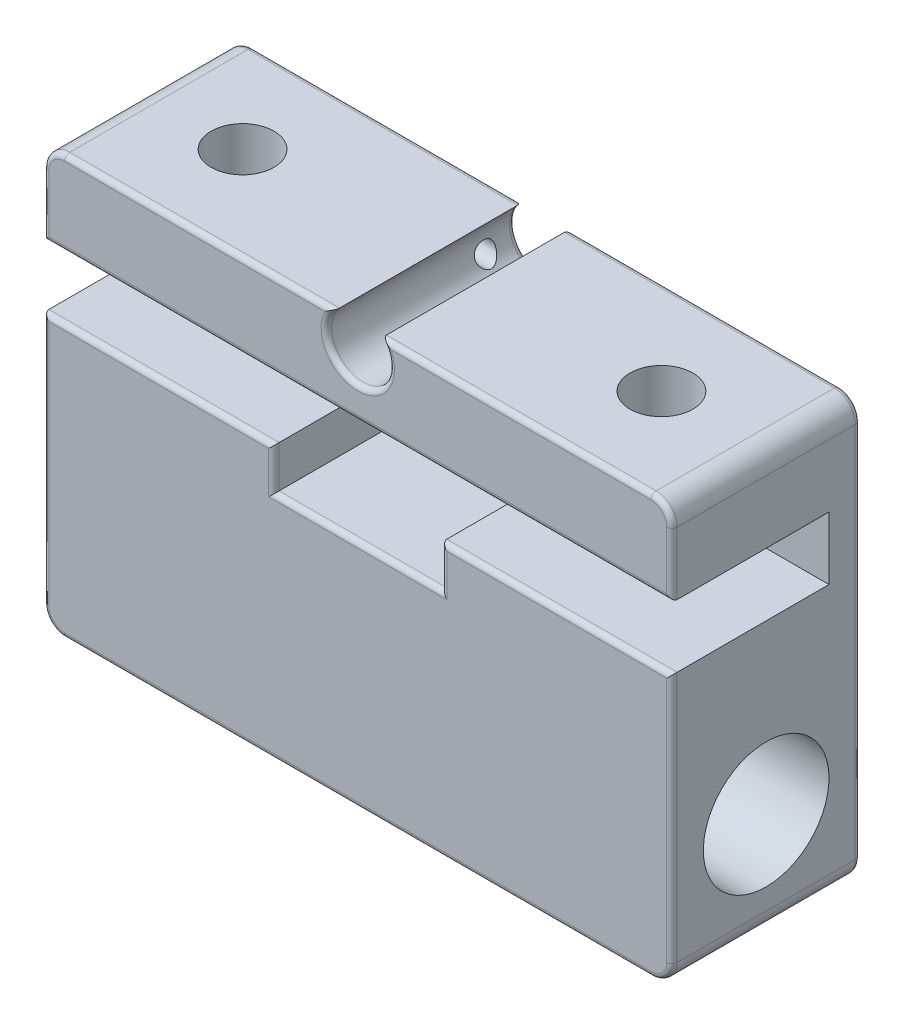
SolidWorks part; units mm, degrees
ref_plane "Front Plane" through (0, 0, 0) normal (0, 0, 1) x (1, 0, 0)
ref_plane "Top Plane" through (0, 0, 0) normal (0, 1, 0) x (1, 0, 0)
ref_plane "Right Plane" through (0, 0, 0) normal (1, 0, 0) x (0, 0, -1)
sketch "Sketch1" plane through (0, 0, 0) normal (0, 0, 1) x (1, 0, 0)
  line L1 (-30, 20) -> (30, 20)
  line L2 (-30, 20) -> (-30, -20)
  line L3 (-30, -20) -> (30, -20)
  line L4 (30, 20) -> (30, -20)
  line L5 (-30, 20) -> (30, -20) construction
  line L6 (-30, -20) -> (30, 20) construction
  point P0 (0, 0)
  dimension "D1" = 40
  dimension "D2" = 60
extrude "Boss-Extrude1" add sketch "Sketch1" along normal mid plane 18
sketch "Sketch2" plane through (-30, 0, 0) normal (-1, 0, 0) x (0, 0, 1)
  line L0 (0, 1.8022) -> (0, -4.9662) construction
  circle A0 centre (0, -10) radius 6
  dimension "D1" = 12
  dimension "D2" = 10
extrude "Cut-Extrude1" cut sketch "Sketch2" against normal through all
sketch "Sketch3" plane through (0, 0, 9) normal (0, 0, 1) x (1, 0, 0)
  line L0 (0, 0) -> (0, 7.3584) construction
  line L4 (30, -20) -> (30, 20)
  line L5 (30, 20) -> (-30, 20)
  line L6 (-30, 20) -> (-30, -20)
  line L7 (-30, -20) -> (30, -20)
  line L8 (30, -20) -> (30, 20) construction
  line L9 (30, 20) -> (-30, 20) construction
  line L10 (-30, 20) -> (-30, -20) construction
  line L11 (-30, -20) -> (30, -20) construction
  circle A0 centre (0, 18) radius 3
  point P7 (0, 0)
  dimension "D2" = 6
  dimension "D3" = 18
  dimension "D1" = 0
extrude "Cut-Extrude2" cut sketch "Sketch3" against normal through all
sketch "Sketch4" plane through (0, 0, 9) normal (0, 0, 1) x (1, 0, 0)
  line L0 (-30, 20) -> (-30, -20) construction
  line L1 (-30, 12) -> (30, 12)
  line L2 (-30, 12) -> (-30, 6)
  line L3 (-30, 6) -> (-8, 6)
  line L4 (30, 12) -> (30, 6)
  line L5 (30, -20) -> (30, 20) construction
  line L6 (8, 6) -> (30, 6)
  line L8 (-8, 6) -> (-8, 2)
  line L9 (-8, 2) -> (8, 2)
  line L10 (8, 6) -> (8, 2)
  dimension "D1" = 6
  dimension "D2" = 16
  dimension "D3" = 8
  dimension "D4" = 12
  dimension "D5" = 4
extrude "Cut-Extrude3" cut sketch "Sketch4" against normal blind 15
sketch "Sketch5" plane through (-30, 0, 0) normal (-1, 0, 0) x (0, 0, 1)
  line L0 (9, 20) -> (9, 12) construction
  line L1 (9, 20) -> (-9, 20) construction
  circle A0 centre (-6, 17) radius 1
  dimension "D1" = 2
  dimension "D2" = 15
  dimension "D3" = 3
extrude "Cut-Extrude4" cut sketch "Sketch5" against normal blind 29
sketch "Sketch6" plane through (-30, 0, 0) normal (-1, 0, 0) x (0, 0, 1)
  circle A0 centre (-6, 17) radius 1.5
  dimension "D1" = 3
extrude "Cut-Extrude5" cut sketch "Sketch6" against normal blind 5
sketch "Sketch7" plane through (0, 20, 0) normal (0, 1, 0) x (1, 0, 0)
  line L0 (-7.4904, 0) -> (6.3865, 0) construction
  line L1 (0, 5.874) -> (0, -4.849) construction
  circle A0 centre (-20, 0) radius 2
  circle A1 centre (20, 0) radius 2
  point P9 (0, 0)
  dimension "D1" = 4
  dimension "D2" = 20
extrude "Cut-Extrude6" cut sketch "Sketch7" against normal up to next
sketch "Sketch8" plane through (0, 20, 0) normal (0, 1, 0) x (1, 0, 0)
  line L0 (0, 5.0067) -> (0, -4.6125) construction
  circle A0 centre (-20, 0) radius 3
  circle A1 centre (20, 0) radius 3
  dimension "D1" = 6
extrude "Cut-Extrude7" cut sketch "Sketch8" against normal blind 5
fillet "Fillet1" radius 2 4 edges at (30, -20, 0) (30, 20, 0) (-30, -20, 0) (-30, 20, 0)
fillet "Fillet2" radius 0.5 28 edges at (29.4142, 19.4142, -9) (15.118, 20, -9) (0, 15, -9) (-15.118, 20, -9) (-29.4142, 19.4142, -9) (-30, 0, -9) (-29.4142, -19.4142, -9) (0, -20, -9) (29.4142, -19.4142, -9) (30, 0, -9) (-29.4142, -19.4142, 9) (-30, -6, 9) (-19, 6, 9) (-8, 4, 9) (0, 2, 9) (8, 4, 9) (19, 6, 9) (30, -6, 9) (29.4142, -19.4142, 9) (0, -20, 9) (0, 12, 9) (-30, 15, 9) (-29.4142, 19.4142, 9) (-15.118, 20, 9) (0, 15, 9) (15.118, 20, 9) (29.4142, 19.4142, 9) (30, 15, 9)
